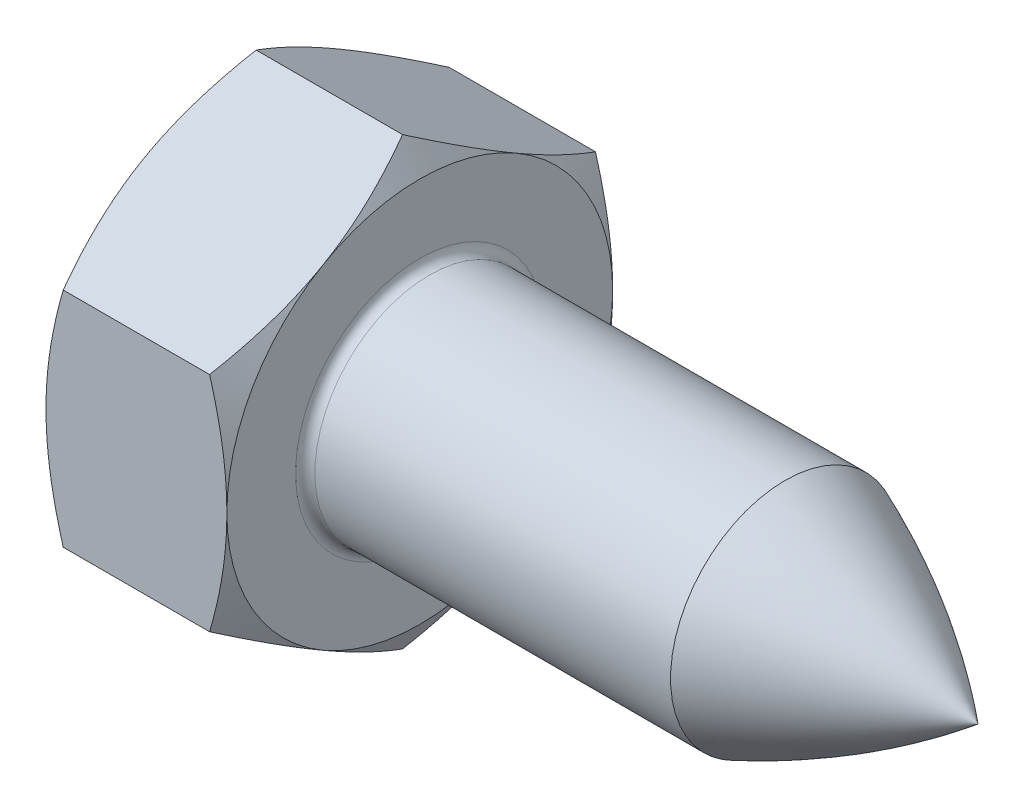
SolidWorks part; units mm, degrees
ref_plane "Front" through (0, 0, 0) normal (0, 0, 1) x (1, 0, 0)
ref_plane "Top" through (0, 0, 0) normal (0, 1, 0) x (1, 0, 0)
ref_plane "Right" through (0, 0, 0) normal (1, 0, 0) x (0, 0, -1)
sketch "Sketch2" plane through (0, 0, 0) normal (1, 0, 0) x (0, 0, -1)
  line L1 (0, 9.2376) -> (-8, 4.6188)
  line L2 (-8, 4.6188) -> (-8, -4.6188)
  line L3 (-8, -4.6188) -> (0, -9.2376)
  line L4 (0, -9.2376) -> (8, -4.6188)
  line L5 (8, -4.6188) -> (8, 4.6188)
  line L6 (8, 4.6188) -> (0, 9.2376)
  circle A0 centre (0, 0) radius 8 construction
extrude "BaseHead" add sketch "Sketch2" along normal blind 7.5
sketch "Sketch1" plane through (0, 0, 0) normal (0, 0, 1) x (1, 0, 0)
  line L0 (-9.5445, 0) -> (41.9665, 0) construction
  line L1 (30.65, 0) -> (30.65, 4.75)
  line L2 (30.65, 4.75) -> (7.5, 4.75)
  line L3 (7.5, 4.75) -> (7.5, 0)
  line L4 (30.65, 0) -> (7.5, 0)
  line L5 (7.5, 4.6188) -> (7.5, -4.6188) construction
  line L6 (9.6, 14.495) -> (9.6, -5.1728) construction
  dimension "l" = 23.15
revolve "BaseBody" add sketch "Sketch1" angle 360 about L0
cosmetic thread "ThreadCosmetic1" [suppressed] parameters "D1"=21.05, "D2"=8.5
sketch "Sketch3" plane through (0, 0, 0) normal (0, 0, 1) x (1, 0, 0)
  line L0 (10.6638, 0) -> (-1.5125, 0) construction
  line L2 (0, 8) -> (0.7145, 9.2376)
  line L5 (0.7145, 9.2376) -> (0, 9.2376)
  line L6 (0, 9.2376) -> (0, 8)
  line L7 (3.75, 9.2376) -> (3.75, 3.7337) construction
  line L8 (7.5, 9.2376) -> (7.5, 8)
  line L9 (6.7855, 9.2376) -> (7.5, 9.2376)
  line L10 (7.5, 8) -> (6.7855, 9.2376)
  dimension "D1" = 16
  dimension "D2" = 30
revolve "Cut-Revolve7" cut sketch "Sketch3" angle 360 about L0
sketch "Sketch7" plane through (0, 0, 0) normal (0, 0, 1) x (1, 0, 0)
  line L0 (0, 0) -> (-8.2734, 0) construction
  line L1 (-0.1, 6.6667) -> (1.5, 6.6667)
  line L2 (-0.1, 6.6667) -> (-0.1, 0)
  line L3 (-0.1, 0) -> (1.5, 0)
  line L4 (1.5, 6.6667) -> (1.5, 0)
  line L5 (7.5, 0) -> (7.5, 6.9282) construction
  dimension "D1" = 0.1
  dimension "D3" = 13.3333
revolve "Cut-Revolve8" cut sketch "Sketch7" angle 360 about L0
sketch "Sketch4" plane through (1.5, -1.1147, 0.1688) normal (-1, 0, 0) x (0, 0, 1)
  line L0 (-9.754, 1.1147) -> (9.3086, 1.1147) construction
  line L1 (-0.1688, 11.4359) -> (-0.1688, -1.847) construction
  line L2 (0.5512, 4.7147) -> (-0.8888, 4.7147)
  line L3 (-0.8888, 4.7147) -> (-0.8888, 1.8347)
  line L4 (-0.8888, 1.8347) -> (-3.7688, 1.8347)
  line L5 (-3.7688, 1.8347) -> (-3.7688, 0.3947)
  line L6 (3.4312, 1.8347) -> (3.4312, 0.3947)
  line L7 (0.5512, 1.8347) -> (3.4312, 1.8347)
  line L8 (0.5512, 4.7147) -> (0.5512, 1.8347)
  line L9 (0.5512, -2.4853) -> (0.5512, 0.3947)
  line L10 (0.5512, 0.3947) -> (3.4312, 0.3947)
  line L11 (-0.8888, 0.3947) -> (-3.7688, 0.3947)
  line L12 (-0.8888, -2.4853) -> (-0.8888, 0.3947)
  line L13 (0.5512, -2.4853) -> (-0.8888, -2.4853)
  point P14 (-0.1688, 4.7147)
  point P17 (3.4312, 1.1147)
  point P18 (-3.7688, 1.1147)
  point P20 (-0.1688, -2.4853)
  dimension "D1" = 1.44
sketch "Sketch9" plane through (7.5, 0, 0) normal (1, 0, 0) x (0, 0, -1)
  point P0 (0, 0)
loft "Cut-Loft1" cut profiles "Sketch9", "Sketch4"
fillet "Fillet1" radius 0.4 1 edges at (7.5, 0, 4.75)
sketch "Sketch5" plane through (0, 0, 0) normal (0, 0, 1) x (1, 0, 0)
  line L0 (31.9782, 0) -> (17.0112, 0) construction
  line L2 (26.45, -4.75) -> (28.55, -4.75)
  line L3 (28.55, -4.75) -> (30.65, -4.225)
  line L5 (30.65, -4.75) -> (30.65, 4.75) construction
  line L6 (26.45, -4.75) -> (26.45, -5.25)
  line L7 (26.45, -5.25) -> (30.65, -5.25)
  line L8 (30.65, -5.25) -> (30.65, -4.225)
  point P15 (28.55, -4.75)
  dimension "D2" = 2.1
  dimension "D4" = 0.5
  dimension "D1" = 9.5
  dimension "D3" = 0.525
revolve "Cut-Revolve1" cut sketch "Sketch5" angle 360 about L0
sketch "Sketch6" plane through (0, 0, 0) normal (0, 0, 1) x (1, 0, 0)
  line L0 (33.3907, 0) -> (10.0621, 0) construction
  line L2 (30.65, -4.75) -> (30.65, 4.75) construction
  line L3 (30.65, 0) -> (22.65, -4.75) construction
  line L6 (30.65, 0) -> (31.15, 0)
  line L7 (22.65, -4.75) -> (30.65, -4.75)
  line L8 (31.15, 0) -> (31.15, -4.75)
  line L9 (31.15, -4.75) -> (30.65, -4.75)
  arc A0 (30.65, 0) -> (22.65, -4.75) centre (10.4863, 24.8481) cw
  dimension "D1" = 32
  dimension "D3" = 9.5
  dimension "D2" = 0.5
revolve "Cut-Revolve6" cut sketch "Sketch6" angle 360 about L0
sketch "Sketch8" plane through (0, 0, 0) normal (0, 0, 1) x (1, 0, 0)
  line L0 (9.35, 5.25) -> (9.85, 5.25)
  line L1 (9.85, 5.25) -> (9.85, 4.75)
  line L2 (9.85, 4.75) -> (9.6, 4.317)
  line L3 (9.6, 4.317) -> (9.35, 4.75)
  line L4 (9.35, 4.75) -> (9.35, 5.25)
  line L5 (0, 0) -> (16.5709, 0) construction
  line L6 (-9.5445, 0) -> (41.9665, 0) construction
  line L7 (7.5, 0) -> (7.5, 6.9282) construction
  dimension "D1" = 9.5
  dimension "D2" = 0.5
  dimension "D3" = 2.1
revolve "Cut-Revolve10" [suppressed] cut sketch "Sketch8" angle 360 about L5
pattern_linear "LPattern10" [suppressed] count 35 spacing 0.6 along (1, 0, 0) of bodies 108
equation "\"D3@Sketch5\" = \"yf@Sketch5\" / 8"
equation "\"D2@ThreadCosmetic1\" = \"st@Sketch1\" - 1"
equation "\"D1@Sketch6\" = \"yc@Sketch6\" * 4"
equation "\"D3@Sketch6\" = \"st@Sketch1\""
equation "\"D2@Sketch5\" = \"yf@Sketch5\" / 2"
equation "\"D1@Sketch3\" = \"s@Sketch2\""
equation "\"D1@Sketch5\" = \"st@Sketch1\""
equation "\"D1@Sketch4\" = \"m@Sketch4\" / 5"
equation "\"D3@Sketch7\" = \"s@Sketch2\" * 5 / 6"
equation "\"D1@ThreadCosmetic1\" = \"l@Sketch1\"  - \"a@Sketch1\""
equation "\"D1@Sketch8\" = \"st@Sketch1\""
equation "\"D2@Sketch8\" =   ( \"st@Sketch1\" - \"D2@ThreadCosmetic1\" )  / 2"
equation "\"D3@Sketch8\" = \"a@Sketch1\""
equation "\"D3@LPattern10\" = \"D2@Sketch8\" * 1.2"
equation "\"D1@LPattern10\" = \"D1@ThreadCosmetic1\" / \"D3@LPattern10\""
